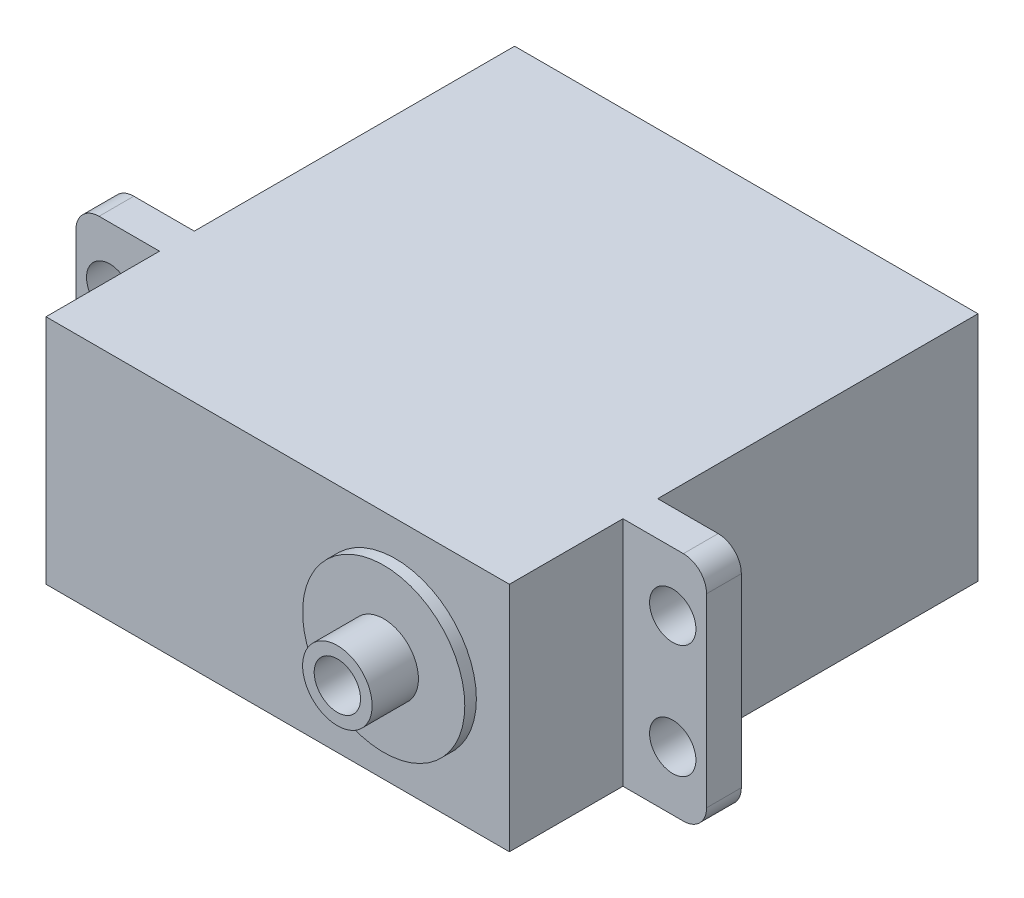
SolidWorks part; units mm, degrees
ref_plane "Front Plane" through (0, 0, 0) normal (0, 0, 1) x (1, 0, 0)
ref_plane "Top Plane" through (0, 0, 0) normal (0, 1, 0) x (1, 0, 0)
ref_plane "Right Plane" through (0, 0, 0) normal (1, 0, 0) x (0, 0, -1)
sketch "Sketch2" plane through (0, 0, 0) normal (0, 0, 1) x (1, 0, 0)
  line L1 (-13.5922, 208.3879) -> (-53.5922, 208.3879)
  line L2 (-13.5922, 208.3879) -> (-13.5922, 228.3879)
  line L3 (-13.5922, 228.3879) -> (-53.5922, 228.3879)
  line L4 (-53.5922, 208.3879) -> (-53.5922, 228.3879)
  dimension "D1" = 40
  dimension "D2" = 20
extrude "Boss-Extrude1" add sketch "Sketch2" along normal blind 27.65
sketch "Sketch3" plane through (0, 0, 27.65) normal (0, 0, 1) x (1, 0, 0)
  line L0 (-53.5922, 208.3879) -> (-13.5922, 208.3879) construction
  line L1 (-6.3722, 208.3879) -> (-60.8122, 208.3879)
  line L2 (-6.3722, 208.3879) -> (-6.3722, 228.3879)
  line L3 (-6.3722, 228.3879) -> (-60.8122, 228.3879)
  line L4 (-60.8122, 208.3879) -> (-60.8122, 228.3879)
  line L5 (-13.5922, 228.3879) -> (-53.5922, 228.3879) construction
  line L6 (-13.5922, 218.3879) -> (-53.5922, 218.3879) construction
  line L7 (-13.5922, 208.3879) -> (-13.5922, 228.3879) construction
  line L8 (-53.5922, 228.3879) -> (-53.5922, 208.3879) construction
  line L9 (-33.5922, 218.3879) -> (-33.5922, 214.2288) construction
  circle A0 centre (-9.2922, 213.4879) radius 2
  circle A1 centre (-9.2922, 223.2879) radius 2
  circle A2 centre (-57.8922, 223.2879) radius 2
  circle A3 centre (-57.8922, 213.4879) radius 2
  dimension "D1" = 0
  dimension "D2" = 0
  dimension "D3" = 54.44
  dimension "D4" = 27.22
extrude "Boss-Extrude2" add sketch "Sketch3" along normal blind 3
sketch "Sketch4" plane through (0, 0, 30.65) normal (0, 0, 1) x (1, 0, 0)
  line L4 (-13.5922, 208.3879) -> (-13.5922, 228.3879)
  line L5 (-53.5922, 208.3879) -> (-13.5922, 208.3879)
  line L6 (-53.5922, 228.3879) -> (-53.5922, 208.3879)
  line L7 (-13.5922, 228.3879) -> (-53.5922, 228.3879)
  line L8 (-13.5922, 208.3879) -> (-13.5922, 228.3879)
  line L9 (-53.5922, 208.3879) -> (-13.5922, 208.3879)
  line L10 (-53.5922, 228.3879) -> (-53.5922, 208.3879)
  line L11 (-13.5922, 228.3879) -> (-53.5922, 228.3879)
  dimension "D1" = 0
extrude "Boss-Extrude3" add sketch "Sketch4" along normal blind 9.8
sketch "Sketch5" plane through (0, 0, 40.45) normal (0, 0, 1) x (1, 0, 0)
  circle A0 centre (-23.4422, 218.3879) radius 7
  circle A1 centre (-57.8922, 223.2879) radius 2 construction
  dimension "D1" = 34.45
extrude "Boss-Extrude4" add sketch "Sketch5" along normal blind 1
sketch "Sketch6" plane through (0, 0, 41.45) normal (0, 0, 1) x (1, 0, 0)
  circle A0 centre (-23.4422, 218.3879) radius 3
extrude "Boss-Extrude5" add sketch "Sketch6" along normal blind 4
fillet "Fillet1" radius 2 4 edges at (-60.8122, 228.3879, 29.15) (-60.8122, 208.3879, 29.15) (-6.3722, 228.3879, 29.15) (-6.3722, 208.3879, 29.15)
sketch "Sketch7" plane through (0, 0, 45.45) normal (0, 0, 1) x (1, 0, 0)
  circle A2 centre (-23.4422, 218.3879) radius 2
  circle A3 centre (-23.4422, 218.3879) radius 2
  dimension "D1" = 1
extrude "Cut-Extrude1" cut sketch "Sketch7" against normal blind 10
